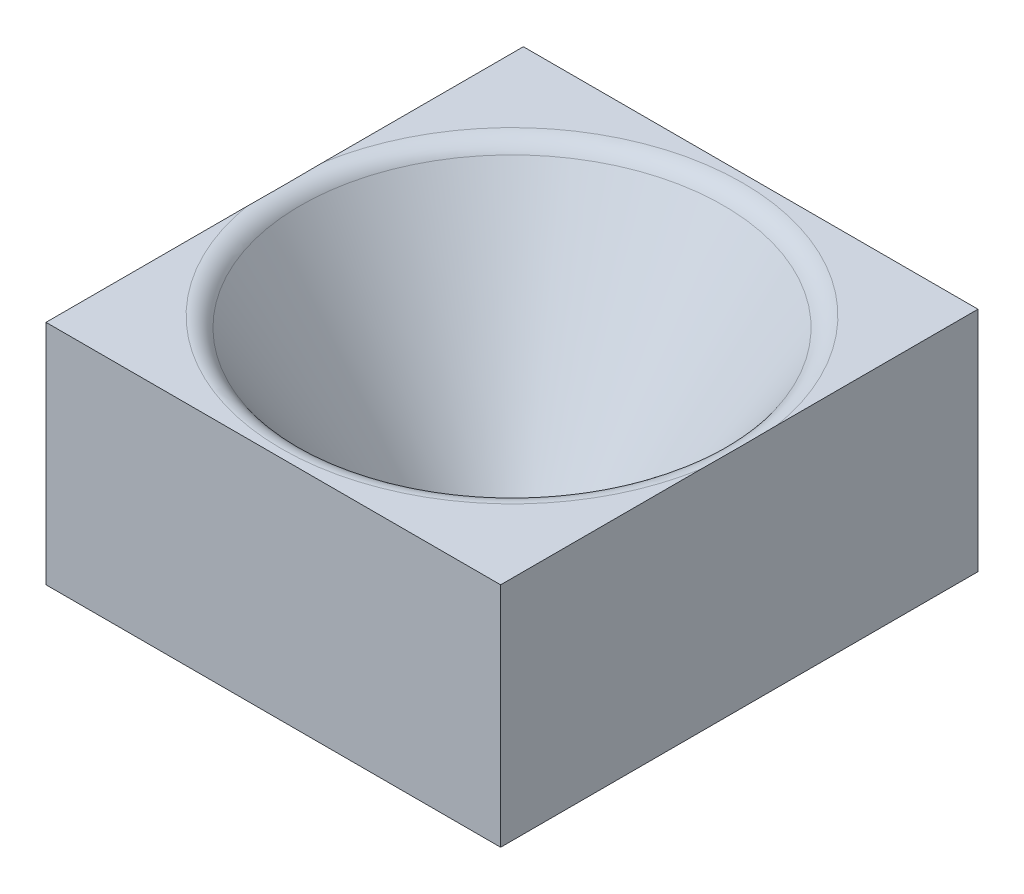
SolidWorks part; units mm, degrees
ref_plane "Front Plane" through (0, 0, 0) normal (0, 0, 1) x (1, 0, 0)
ref_plane "Top Plane" through (0, 0, 0) normal (0, 1, 0) x (1, 0, 0)
ref_plane "Right Plane" through (0, 0, 0) normal (1, 0, 0) x (0, 0, -1)
sketch "Sketch1" plane through (0, 0, 0) normal (0, 1, 0) x (1, 0, 0)
  line L0 (0, -81.1722) -> (0, 92.799) construction
  line L1 (-50, 52.5) -> (50, 52.5)
  line L2 (-50, 52.5) -> (-50, -52.5)
  line L3 (-50, -52.5) -> (50, -52.5)
  line L4 (50, 52.5) -> (50, -52.5)
  line L5 (-86.3397, 0) -> (134.3541, 0) construction
  dimension "D1" = 100
  dimension "D2" = 105
extrude "Boss-Extrude1" add sketch "Sketch1" along normal blind 50
sketch "Sketch5" plane through (0, 0, 0) normal (1, 0, 0) x (0, 0, -1)
  line L0 (0, -20.2311) -> (0, 46.6063) construction
  line L1 (-48, 50) -> (-15, 0)
  line L2 (-52.5, 0) -> (52.5, 0) construction
  line L3 (-15, 0) -> (0, 0)
  line L4 (0, 0) -> (0, 50)
  line L5 (-52.5, 50) -> (52.5, 50) construction
  line L6 (0, 50) -> (-48, 50)
  point P14 (-45.2154, 30)
  dimension "D1" = 15
  dimension "D3" = 48
revolve "Cut-Revolve1" cut sketch "Sketch5" angle 360 about L0
fillet "Fillet1" radius 5 1 edges at (0, 50, -48)
sketch "Sketch8" plane through (0, 0, 0) normal (0, -1, 0) x (1, 0, 0)
  line L0 (0, 0) -> (0, 56.1231) construction
  line L1 (-17.3, 48.5733) -> (5.2, 48.5733)
  line L2 (-17.3, 48.5733) -> (-17.3, 36.0733)
  line L3 (-17.3, 36.0733) -> (5.2, 36.0733)
  line L4 (5.2, 48.5733) -> (5.2, 36.0733)
  dimension "D1" = 22.5
  dimension "D2" = 12.5
  dimension "D3" = 5.2
extrude "Cut-Extrude4" cut sketch "Sketch8" against normal blind 30
sketch "Sketch9" plane through (0, 0, 0) normal (0, -1, 0) x (1, 0, 0)
  line L0 (5.2, 48.5733) -> (-17.3, 48.5733) construction
  line L1 (-22.8, 48.5733) -> (10.7, 48.5733)
  line L2 (-22.8, 48.5733) -> (-22.8, 36.0733)
  line L3 (-22.8, 36.0733) -> (10.7, 36.0733)
  line L4 (10.7, 48.5733) -> (10.7, 36.0733)
  line L5 (-17.3, 36.0733) -> (5.2, 36.0733) construction
  line L6 (-17.3, 48.5733) -> (-17.3, 36.0733) construction
  line L7 (5.2, 36.0733) -> (5.2, 48.5733) construction
  dimension "D1" = 5.5
  dimension "D2" = 5.5
extrude "Cut-Extrude5" cut sketch "Sketch9" against normal blind 12
